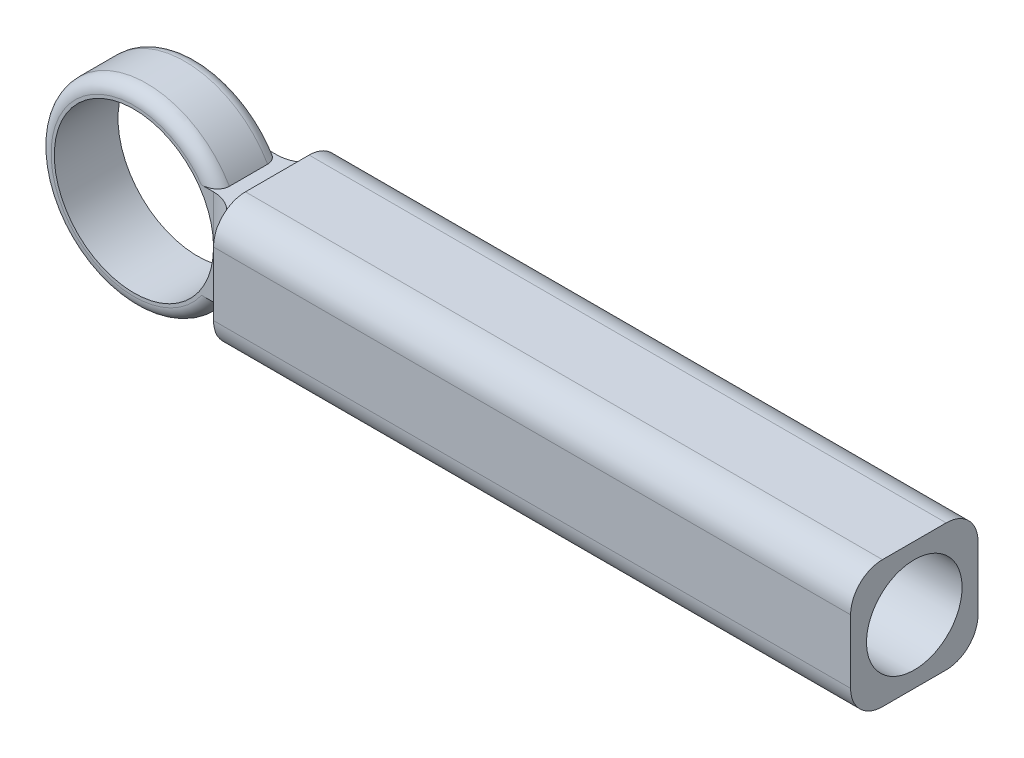
SolidWorks part; units mm, degrees
ref_plane "Plan de face" through (0, 0, 0) normal (0, 0, 1) x (1, 0, 0)
ref_plane "Plan de dessus" through (0, 0, 0) normal (0, 1, 0) x (1, 0, 0)
ref_plane "Plan de droite" through (0, 0, 0) normal (1, 0, 0) x (0, 0, -1)
sketch "Esquisse1" plane through (0, 0, 0) normal (0, 0, 1) x (1, 0, 0)
  line L0 (0, 0) -> (3.5, 0) construction
  line L2 (2.5981, 1.5) -> (3.5, 1.5)
  line L3 (3.5, 1.5) -> (3.5, -1.5)
  line L4 (3.5, -1.5) -> (2.5981, -1.5)
  arc A0 (2.5981, 1.5) -> (2.5981, -1.5) centre (0, 0) ccw
  circle A1 centre (0, 0) radius 2.5
  dimension "D1" = 5
  dimension "D2" = 6
  dimension "D3" = 3.5
  dimension "D4" = 3
extrude "Boss.-Extru.1" add sketch "Esquisse1" along normal blind 2
sketch "Esquisse2" plane through (3.5, 0, 0) normal (1, 0, 0) x (0, 0, -1)
  line L0 (0, 0) -> (-2, 0) construction
  line L2 (-2, -1.5) -> (-2, 1.5) construction
  line L8 (-3, -2) -> (1, -2)
  line L9 (-3, -2) -> (-3, 2)
  line L10 (-3, 2) -> (1, 2)
  line L11 (1, -2) -> (1, 2)
  line L12 (-3, -2) -> (1, 2) construction
  line L13 (-3, 2) -> (1, -2) construction
  point P6 (-1, 0)
  dimension "D1" = 4
  dimension "D2" = 4
extrude "Boss.-Extru.2" add sketch "Esquisse2" along normal blind 20
sketch "Esquisse3" plane through (23.5, 0, 0) normal (1, 0, 0) x (0, 0, -1)
  circle A0 centre (-1, 0) radius 1.5
  dimension "D1" = 3
extrude "Enlèv. mat.-Extru.2" cut sketch "Esquisse3" against normal blind 18.5
fillet "Congé1" radius 1 6 edges at (13.5, -2, 3) (13.5, -2, -1) (13.5, 2, -1) (13.5, 2, 3) (3.5, 0, 0) (3.5, 0, 2)
fillet "Congé2" radius 0.4 2 edges at (-3, 0, 2) (-3, 0, 0)
ref_plane "Plan1" through (0, 0, 1) normal (0, 0, 1) x (1, 0, 0)
sketch "Esquisse4" plane through (0, 0, 1) normal (0, 0, 1) x (1, 0, 0)
  circle A0 centre (0, 0) radius 2.5 construction
  circle A2 centre (0, 0) radius 2.5 construction
